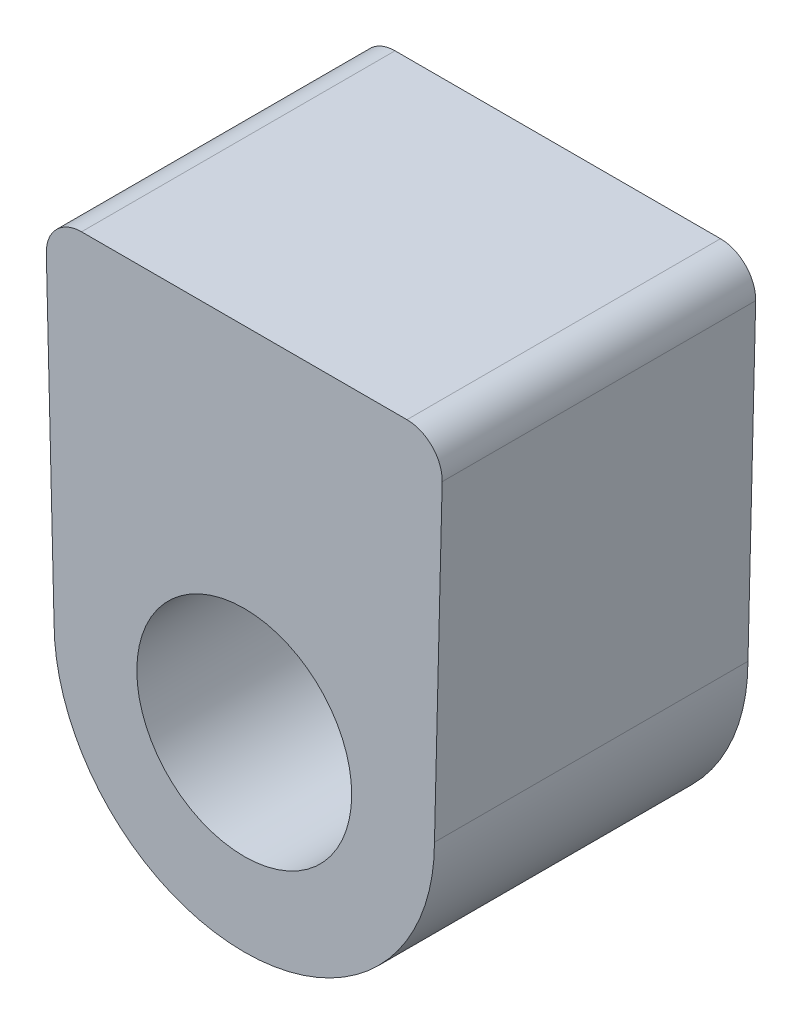
SolidWorks part; units mm, degrees
material "POM copolymère d'acétal"
ref_plane "Front Plane" through (0, 0, 0) normal (0, 0, 1) x (1, 0, 0)
ref_plane "Top Plane" through (0, 0, 0) normal (0, 1, 0) x (1, 0, 0)
ref_plane "Right Plane" through (0, 0, 0) normal (1, 0, 0) x (0, 0, -1)
sketch "Sketch1" plane through (0, 0, 0) normal (0, 0, 1) x (1, 0, 0)
  line L0 (-5.4, 0) -> (-5.6444, 10)
  line L1 (-5.6444, 10) -> (5.6444, 10)
  line L2 (5.6444, 10) -> (5.4, 0)
  line L3 (0, 10) -> (0, -5.4) construction
  arc A0 (-5.4, 0) -> (5.4, 0) centre (0, 0) ccw
  circle A1 centre (0, 0) radius 3.05
  dimension "D2" = 5.4
  dimension "D3" = 6.1
  dimension "D1" = 2.8
  dimension "D4" = 10
extrude "Boss-Extrude1" add sketch "Sketch1" along normal blind 4.45 and the other way blind 4.45
hole_wizard "Tap Drill for M1.6 Tap1" positions "Sketch3" profile "Sketch2" hole size "M1.6" standard "DIN"
sketch "Sketch3" plane through (0, 0, -4.45) normal (0, 0, -1) x (-1, 0, 0)
  line L0 (0, 0) -> (0, 10) construction
  line L1 (-5.6444, 10) -> (5.6444, 10) construction
  point P0 (-2.5, 7.75)
  point P26 (2.5, 7.75)
  dimension "D1" = 2.5
  dimension "D2" = 7.75
sketch "Sketch2" plane through (2.5, 7.75, -4.45) normal (1, 0, 0) x (0, 1, 0)
  line L0 (0, 0) -> (0, 5)
  line L1 (0, 5) -> (0.625, 5)
  line L2 (0.625, 5) -> (0.625, 0)
  line L5 (0.625, 0) -> (0, 0)
  line L10 (0, 5) -> (-0.625, 5) construction
  line L11 (0, -6.35) -> (0, 107.95) construction
  dimension "Hole Dia." = 1.25
  dimension "Hole Depth" = 5
  dimension "Drill Angle" = 180
fillet "Fillet1" radius 1 2 edges at (-5.6444, 10, 0) (5.6444, 10, 0)
